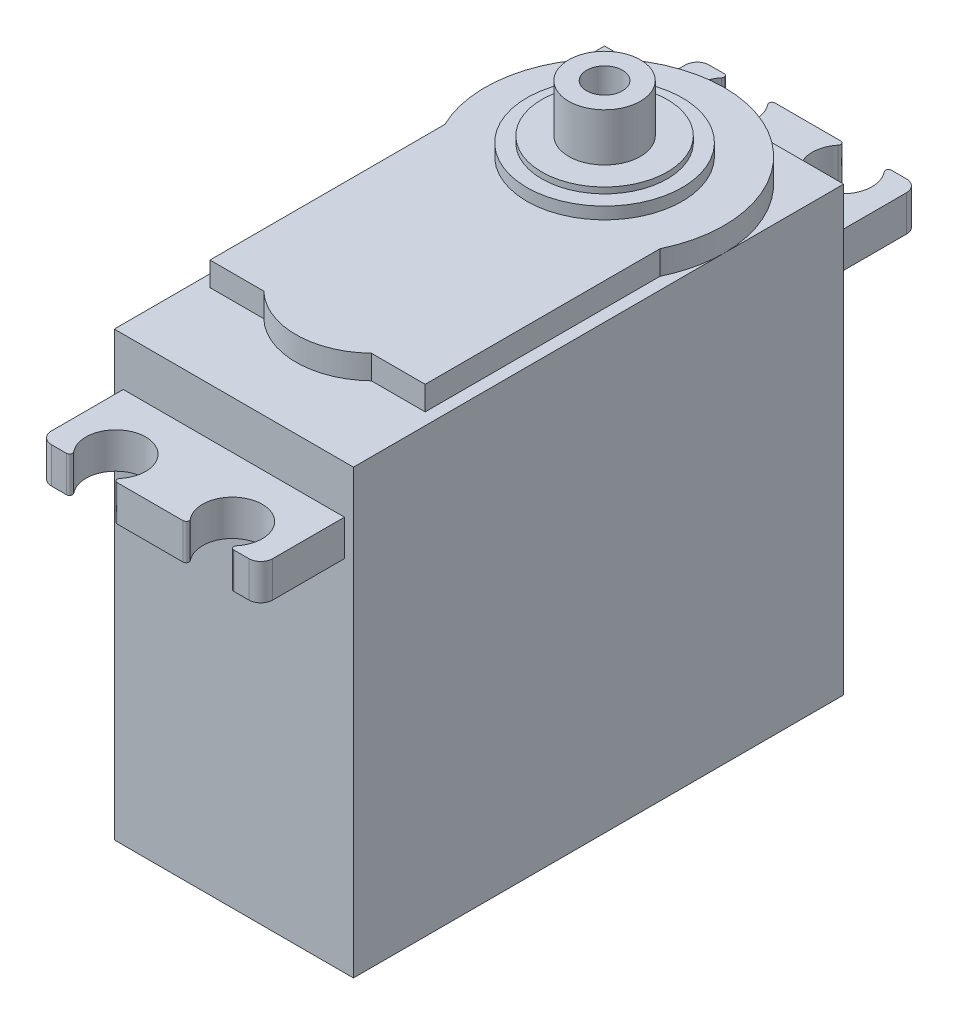
SolidWorks part; units mm, degrees
ref_plane "Front Plane" through (0, 0, 0) normal (0, 0, 1) x (1, 0, 0)
ref_plane "Top Plane" through (0, 0, 0) normal (0, 1, 0) x (1, 0, 0)
ref_plane "Right Plane" through (0, 0, 0) normal (1, 0, 0) x (0, 0, -1)
sketch "Sketch1" plane through (0, 0, 0) normal (0, 1, 0) x (1, 0, 0)
  line L1 (-10, -20.5) -> (10, -20.5)
  line L2 (-10, -20.5) -> (-10, 20.5)
  line L3 (-10, 20.5) -> (10, 20.5)
  line L4 (10, -20.5) -> (10, 20.5)
  line L5 (-10, -20.5) -> (10, 20.5) construction
  line L6 (-10, 20.5) -> (10, -20.5) construction
  point P0 (0, 0)
  dimension "D1" = 41
  dimension "D2" = 20
extrude "Boss-Extrude1" add sketch "Sketch1" along normal blind 37
sketch "Sketch2" plane through (0, 37, 0) normal (0, 1, 0) x (1, 0, 0)
  line L0 (0, 20.5) -> (0, 0.5) construction
  line L1 (10, 20.5) -> (-10, 20.5) construction
  line L2 (0, 10.5) -> (-10, 10.5) construction
  line L3 (-10, 20.5) -> (-10, -20.5) construction
  line L4 (0, 10.5) -> (10, 10.5) construction
  line L5 (10, -20.5) -> (10, 20.5) construction
  line L6 (0, 10.5) -> (0, -13.5)
  line L7 (-9, 10.5) -> (-9, -13.5)
  line L8 (9, 10.5) -> (9, -13.5)
  line L9 (-9, -13.5) -> (9, -13.5)
  line L10 (9, -13.5) -> (4.5, -13.5)
  line L11 (-9, -13.5) -> (-4.5, -13.5)
  circle A0 centre (0, 10.5) radius 10
  circle A1 centre (0, -8.8096) radius 6.5
  dimension "D5" = 13
  dimension "D1" = 20
  dimension "D4" = 34
  dimension "D6" = 4.5
  dimension "D7" = 4.5
  dimension "D2" = 9
  dimension "D3" = 9
extrude "Boss-Extrude2" add sketch "Sketch2" along normal blind 2 contours A0 | A1 L9 L8 A0 L6 | L9 A1 L6 | L6 A1 L9 | A1 L6 A0 L7 L9 | L9 A1 region at (6.1891, 37, 3.5714) region at (-6.1891, 37, 3.5714) region at (-5.1607, 37, -2.2665) region at (2.8541, 37, 8.3097) region at (-2.8541, 37, 8.3097) region at (0, 37, 14.2332)
sketch "Sketch3" plane through (0, 39, 0) normal (0, 1, 0) x (1, 0, 0)
  circle A0 centre (0, 10.5) radius 6.5
  dimension "D1" = 13
extrude "Boss-Extrude3" add sketch "Sketch3" along normal blind 1
sketch "Sketch4" plane through (0, 40, 0) normal (0, 1, 0) x (1, 0, 0)
  circle A0 centre (0, 10.5) radius 5.25
  dimension "D1" = 10.5
extrude "Boss-Extrude4" add sketch "Sketch4" along normal blind 0.5
sketch "Sketch5" plane through (0, 40.5, 0) normal (0, 1, 0) x (1, 0, 0)
  circle A0 centre (0, 10.5) radius 3
  dimension "D1" = 6
extrude "Boss-Extrude5" add sketch "Sketch5" along normal blind 4
sketch "Sketch6" plane through (0, 0, -20.5) normal (0, 0, -1) x (-1, 0, 0)
  line L0 (0, 0) -> (0, 3)
  line L1 (0, 3) -> (0, 7.5)
  line L3 (-3.5, 3) -> (3.5, 3)
  line L4 (-3.5, 3) -> (-3.5, 7.5)
  line L5 (-3.5, 7.5) -> (3.5, 7.5)
  line L6 (3.5, 3) -> (3.5, 7.5)
  line L7 (-3.5, 3) -> (3.5, 7.5) construction
  line L8 (-3.5, 7.5) -> (3.5, 3) construction
  point P3 (0, 5.25)
  dimension "D1" = 3
  dimension "D2" = 4.5
  dimension "D3" = 7
  dimension "D4" = 4.5
extrude "Boss-Extrude6" add sketch "Sketch6" along normal blind 5.5 contours L5 L4 L3 L1 | L3 L6 L5 L1 region at (1.75, 5.25, -20.5) region at (-1.75, 5.25, -20.5)
sketch "Sketch7" plane through (0, 0, -26) normal (0, 0, -1) x (-1, 0, 0)
  line L0 (0, 7.5) -> (0, 3)
  line L1 (-3.5, 7.5) -> (3.5, 7.5) construction
  line L2 (-3.5, 3) -> (3.5, 3) construction
  line L4 (-2.75, 3.5) -> (2.75, 3.5)
  line L5 (-2.75, 3.5) -> (-2.75, 7)
  line L6 (-2.75, 7) -> (2.75, 7)
  line L7 (2.75, 3.5) -> (2.75, 7)
  line L8 (-2.75, 3.5) -> (2.75, 7) construction
  line L9 (-2.75, 7) -> (2.75, 3.5) construction
  line L10 (-3.5, 3) -> (3.5, 3)
  line L11 (-3.5, 3) -> (-3.5, 7.5)
  line L12 (-3.5, 7.5) -> (3.5, 7.5)
  line L13 (3.5, 3) -> (3.5, 7.5)
  line L14 (-3.5, 3) -> (3.5, 7.5) construction
  line L15 (-3.5, 7.5) -> (3.5, 3) construction
  point P6 (0, 5.25)
  point P11 (0, 5.25)
  line M3 (3.5, 7.5) -> (-3.5, 7.5)
  line M4 (-3.5, 7.5) -> (-3.5, 3)
  line M5 (-3.5, 3) -> (3.5, 3)
  line M6 (3.5, 3) -> (3.5, 7.5)
  dimension "D1" = 3.5
  dimension "D2" = 5.5
extrude "Cut-Extrude1" cut sketch "Sketch7" against normal blind 5 contours L7 L4 L0 L6 M5 M6 M3 | L5 L6 L0 L4 M3 M4 M5 region at (-1.75, 7.443, -26) region at (0.057, 7.25, -26)
sketch "Sketch8" plane through (0, 0, 20.5) normal (0, 0, 1) x (1, 0, 0)
  line L0 (0, 0) -> (0, 30)
  line L1 (0, 30) -> (10, 30)
  line L2 (10, 37) -> (10, 0) construction
  line L3 (10, 30) -> (-10, 30)
  line L4 (-10, 37) -> (-10, 0) construction
  line L5 (0, 30) -> (0, 33)
  line L6 (0, 33) -> (-10, 33)
  line L7 (-10, 33) -> (10, 33)
  line L8 (0, 33) -> (0, 30)
  line L9 (9.25, 30) -> (9.25, 33)
  line L10 (-9.25, 30) -> (-9.25, 33)
  dimension "D1" = 30
  dimension "D2" = 3
  dimension "D3" = 9.25
  dimension "D4" = 9.25
extrude "Boss-Extrude7" add sketch "Sketch8" along normal blind 7 contours L1 L9 L7 L5 | L10 L3 L5 L6 region at (4.625, 31.5, 20.5) region at (-4.625, 31.5, 20.5)
sketch "Sketch9" plane through (0, 0, -20.5) normal (0, 0, -1) x (-1, 0, 0)
  line L4 (-9.25, 30) -> (9.25, 30)
  line L5 (-9.25, 33) -> (-9.25, 30)
  line L6 (9.25, 33) -> (-9.25, 33)
  line L7 (9.25, 30) -> (9.25, 33)
  line L8 (-9.25, 30) -> (9.25, 30)
  line L9 (-9.25, 33) -> (-9.25, 30)
  line L10 (9.25, 33) -> (-9.25, 33)
  line L11 (9.25, 30) -> (9.25, 33)
  dimension "D1" = 0
extrude "Boss-Extrude8" add sketch "Sketch9" along normal blind 7
fillet "Fillet1" radius 1 4 edges at (-9.25, 31.5, 27.5) (9.25, 31.5, 27.5) (9.25, 31.5, -27.5) (-9.25, 31.5, -27.5)
sketch "Sketch10" plane through (0, 33, 0) normal (0, 1, 0) x (1, 0, 0)
  line L0 (0, 20.5) -> (0, 25.5)
  line L1 (0, 25.5) -> (7.25, 25.5)
  line L2 (0, 25.5) -> (-7.25, 25.5)
  line L3 (0, 25.5) -> (2.5, 25.5)
  line L4 (0, 25.5) -> (-2.5, 25.5)
  line L5 (0, 25.5) -> (2.5, 25.5)
  line L6 (-2.5, 25.5) -> (-7.25, 25.5)
  line L7 (0, 20.5) -> (0, -20.5) construction
  line L8 (-10, -20.5) -> (10, -20.5) construction
  line L9 (0, 0) -> (4.875, 0) construction
  arc A0 (9, 6.1411) -> (-9, 6.1411) centre (0, 10.5) ccw construction
  circle A1 centre (-4.875, 25.5) radius 2.5
  circle A2 centre (4.875, 25.5) radius 2.5
  circle A3 centre (4.875, -25.5) radius 2.5
  circle A4 centre (-4.875, -25.5) radius 2.5
  dimension "D6" = 5
  dimension "D1" = 7.25
  dimension "D2" = 7.25
  dimension "D3" = 2.5
  dimension "D4" = 2.5
  dimension "D5" = 5
extrude "Cut-Extrude2" cut sketch "Sketch10" against normal blind 7 contours A3 | A4 | A1 | A2 region at (4.875, 33, -25.3791) region at (-4.875, 33, -25.3791) region at (4.875, 33, 25.5) region at (-4.875, 33, 25.5)
sketch "Sketch11" plane through (0, 44.5, 0) normal (0, 1, 0) x (1, 0, 0)
  circle A0 centre (0, 10.5) radius 1.5
  dimension "D1" = 3
extrude "Cut-Extrude3" cut sketch "Sketch11" against normal blind 20
fillet "Fillet2" radius 0.25 8 edges at (-6.375, 31.5, -27.5) (3.375, 31.5, -27.5) (6.375, 31.5, -27.5) (-3.375, 31.5, -27.5) (-6.375, 31.5, 27.5) (-3.375, 31.5, 27.5) (3.375, 31.5, 27.5) (6.375, 31.5, 27.5)
fillet "Fillet3" radius 2 4 edges at (2.75, 7, -23.5) (-2.75, 7, -23.5) (-2.75, 3.5, -23.5) (2.75, 3.5, -23.5)
